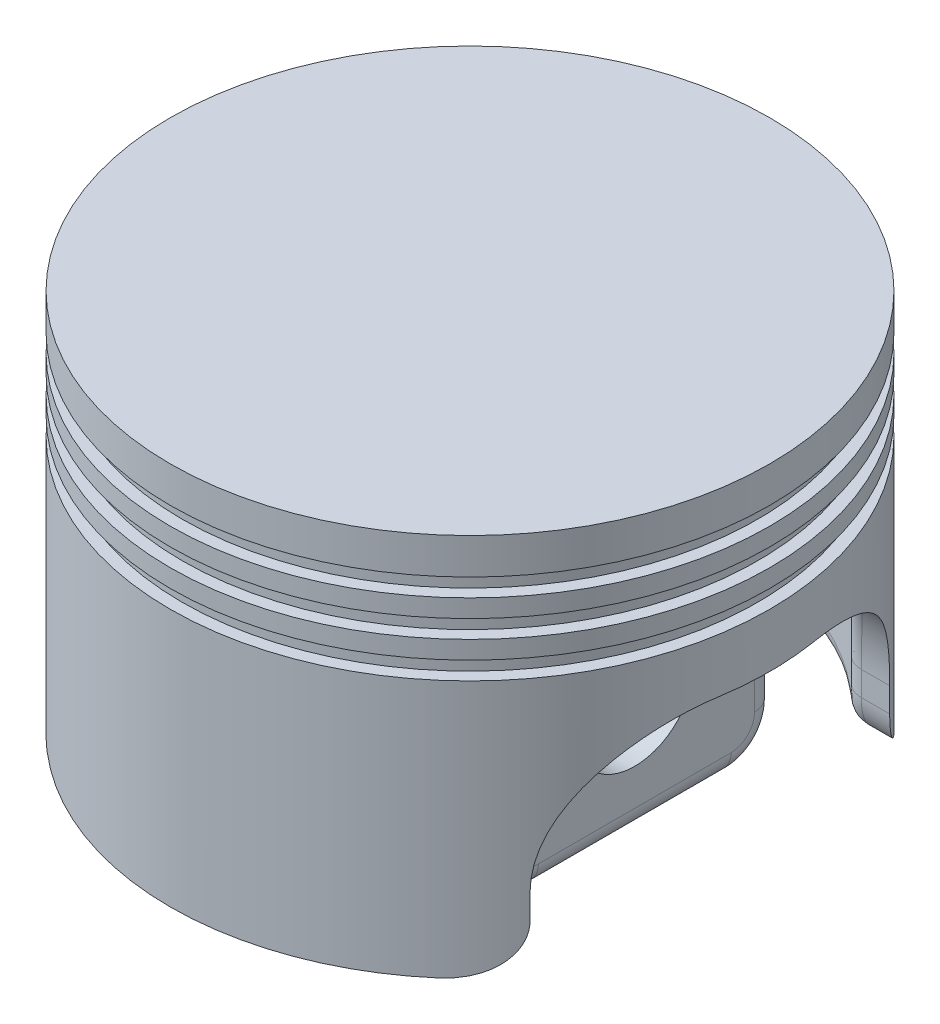
SolidWorks part; units mm, degrees
ref_plane "Front Plane" through (0, 0, 0) normal (0, 0, 1) x (1, 0, 0)
ref_plane "Top Plane" through (0, 0, 0) normal (0, 1, 0) x (1, 0, 0)
ref_plane "Right Plane" through (0, 0, 0) normal (1, 0, 0) x (0, 0, -1)
sketch "Sketch2" plane through (0, 0, 0) normal (0, 0, 1) x (1, 0, 0)
  line L0 (0, 0) -> (63.5, 0)
  line L1 (63.5, 0) -> (63.5, -81.28)
  line L2 (63.5, -81.28) -> (57.15, -81.28)
  line L3 (57.15, -81.28) -> (57.15, -19)
  line L4 (57.15, -19) -> (0, -19)
  line L5 (0, -19) -> (0, 0)
  dimension "D1" = 63.5
  dimension "D2" = 81.28
  dimension "D3" = 19
  dimension "D4" = 57.15
revolve "Revolve1" add sketch "Sketch2" angle 360 about L5
sketch "Sketch3" plane through (0, 0, 0) normal (1, 0, 0) x (0, 0, -1)
  line L0 (-63.5, -81.28) -> (63.5, -81.28) construction
  line L1 (-38.1, -38.1) -> (38.1, -38.1)
  line L2 (-38.1, -38.1) -> (-38.1, -81.28)
  line L3 (-38.1, -81.28) -> (38.1, -81.28)
  line L4 (38.1, -38.1) -> (38.1, -81.28)
  line L5 (-38.1, -38.1) -> (38.1, -81.28) construction
  line L6 (-38.1, -81.28) -> (38.1, -38.1) construction
  point P0 (0, -59.69)
  point P5 (0, 0)
  point P6 (0, 0)
  point P7 (0, 0)
  dimension "D1" = 76.2
  dimension "D2" = 43.18
extrude "Cut-Extrude1" cut sketch "Sketch3" against normal through all both and the other way through all
sketch "Sketch4" plane through (0, 0, 0) normal (1, 0, 0) x (0, 0, -1)
  line L0 (0, 0) -> (0, -27.3101) construction
  line L1 (63.5, -81.28) -> (63.5, 0) construction
  line L2 (60.96, -7.62) -> (66.04, -7.62)
  line L3 (60.96, -7.62) -> (60.96, -11.43)
  line L4 (60.96, -11.43) -> (66.04, -11.43)
  line L5 (66.04, -7.62) -> (66.04, -11.43)
  line L6 (60.96, -7.62) -> (66.04, -11.43) construction
  line L7 (60.96, -11.43) -> (66.04, -7.62) construction
  line L8 (63.5, 0) -> (-63.5, 0) construction
  point P3 (63.5, -9.525)
  dimension "D1" = 3.81
  dimension "D2" = 2.54
  dimension "D3" = 7.62
revolve "Cut-Revolve1" cut sketch "Sketch4" angle 360 about L0
pattern_linear "LPattern1" count 3 spacing 7.62 along (0, -1, 0) of "Cut-Revolve1"
sketch "Sketch5" plane through (0, -19, 0) normal (0, -1, 0) x (1, 0, 0)
  line L0 (0, 0) -> (0, 33.9935) construction
  line L1 (34.88, -30.4) -> (15.88, -30.4)
  line L2 (-34.88, 30.4) -> (-15.88, 30.4)
  line L3 (-34.88, 30.4) -> (-34.88, -30.4)
  line L4 (-34.88, -30.4) -> (-15.88, -30.4)
  line L5 (-15.88, 30.4) -> (-15.88, -30.4)
  line L6 (-34.88, 30.4) -> (-15.88, -30.4) construction
  line L7 (-34.88, -30.4) -> (-15.88, 30.4) construction
  line L8 (34.88, 30.4) -> (15.88, 30.4)
  line L9 (15.88, 30.4) -> (15.88, -30.4)
  line L10 (34.88, 30.4) -> (34.88, -30.4)
  point P3 (-25.38, 0)
  dimension "D1" = 19
  dimension "D2" = 60.8
  dimension "D3" = 31.76
extrude "Boss-Extrude1" add sketch "Sketch5" along normal blind 63.5
sketch "Sketch6" plane through (34.88, 0, 0) normal (1, 0, 0) x (0, 0, -1)
  line L0 (30.4, -82.5) -> (-30.4, -82.5) construction
  circle A0 centre (0, -57.1) radius 12.7
  dimension "D1" = 25.4
  dimension "D2" = 25.4
extrude "Cut-Extrude2" cut sketch "Sketch6" against normal through all
fillet "Fillet1" radius 28 4 edges at (-46.6985, -38.1, -38.1) (-46.6985, -38.1, 38.1) (46.6985, -38.1, -38.1) (46.6985, -38.1, 38.1)
fillet "Fillet2" radius 10 8 edges at (-46.6985, -81.28, -38.1) (46.6985, -81.28, -38.1) (46.6985, -81.28, 38.1) (-46.6985, -81.28, 38.1) (25.38, -82.5, 30.4) (25.38, -82.5, -30.4) (-25.38, -82.5, 30.4) (-25.38, -82.5, -30.4)
fillet "Fillet3" radius 5 36 edges at (34.88, -45.75, -30.4) (34.88, -79.5711, -27.4711) (34.88, -45.75, 30.4) (34.88, -79.5711, 27.4711) (15.88, -45.75, 30.4) (15.88, -79.5711, 27.4711) (15.88, -45.75, -30.4) (15.88, -79.5711, -27.4711) (-15.88, -45.75, -30.4) (-15.88, -79.5711, -27.4711) (-15.88, -45.75, 30.4) (-15.88, -79.5711, 27.4711) (-34.88, -45.75, 30.4) (-34.88, -79.5711, 27.4711) (-34.88, -45.75, -30.4) (-34.88, -79.5711, -27.4711) (41.3657, -76.2692, 39.4335) (42.5971, -68.69, 38.1) (50.4318, -43.6881, 26.8841) (57.15, -38.1, 0) (46.055, -51.2516, -33.8387) (42.5971, -68.69, -38.1) (40.0022, -78.1316, -40.816) (0, -81.28, -57.15) (-41.3657, -76.2692, -39.4335) (-42.5971, -68.69, -38.1) (-50.4318, -43.6881, -26.8841) (-57.15, -38.1, 0) (-46.055, -51.2516, 33.8387) (-42.5971, -68.69, 38.1) (-40.0022, -78.1316, 40.816) (34.88, -82.5, 0) (15.88, -82.5, 0) (-15.88, -82.5, 0) (-34.88, -82.5, 0) (0, -81.28, 57.15)
fillet "Fillet4" radius 5 17 edges at (17.3445, -19, 28.9355) (15.88, -19, 0) (17.3445, -19, -28.9355) (25.38, -19, -30.4) (33.4155, -19, -28.9355) (34.88, -19, 0) (33.4155, -19, 28.9355) (25.38, -19, 30.4) (-33.4155, -19, 28.9355) (-34.88, -19, 0) (-33.4155, -19, -28.9355) (-25.38, -19, -30.4) (-17.3445, -19, -28.9355) (-15.88, -19, 0) (-17.3445, -19, 28.9355) (-25.38, -19, 30.4) (0, -19, -57.15)
